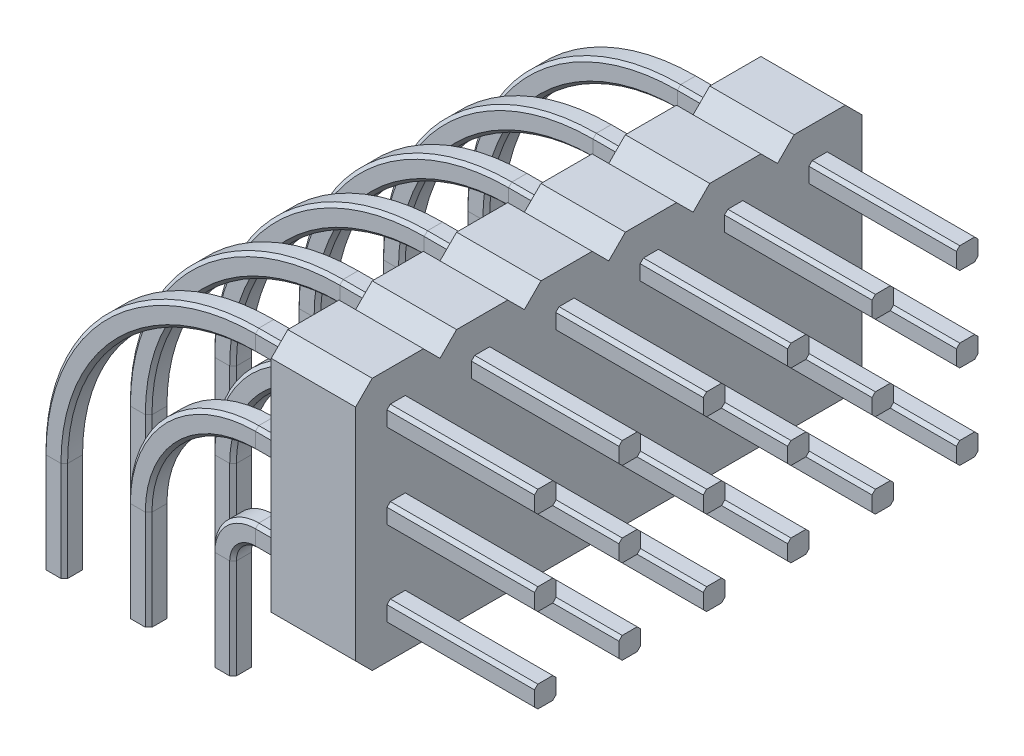
SolidWorks part; units mm, degrees
ref_plane "Front Plane" through (0, 0, 0) normal (0, 0, 1) x (1, 0, 0)
ref_plane "Top Plane" through (0, 0, 0) normal (0, 1, 0) x (1, 0, 0)
ref_plane "Right Plane" through (0, 0, 0) normal (1, 0, 0) x (0, 0, -1)
sketch "Sketch1" plane through (0, 0, 0) normal (0, 1, 0) x (1, 0, 0)
  line L0 (0.225, 0.325) -> (0.325, 0.225)
  line L1 (-0.225, 0.325) -> (0.225, 0.325)
  line L2 (-0.325, 0.225) -> (-0.325, -0.225)
  line L3 (-0.225, -0.325) -> (0.225, -0.325)
  line L4 (0.325, 0.225) -> (0.325, -0.225)
  line L5 (-0.325, 0.325) -> (0.325, -0.325) construction
  line L6 (-0.325, -0.325) -> (0.325, 0.325) construction
  line L7 (-0.325, 0.225) -> (-0.225, 0.325)
  line L8 (-0.325, -0.225) -> (-0.225, -0.325)
  line L9 (0.225, -0.325) -> (0.325, -0.225)
  line L10 (2.215, 0.225) -> (2.215, -0.225)
  line L11 (2.215, 0.225) -> (2.315, 0.325)
  line L12 (2.315, 0.325) -> (2.765, 0.325)
  line L13 (2.765, 0.325) -> (2.865, 0.225)
  line L14 (2.865, 0.225) -> (2.865, -0.225)
  line L15 (2.765, -0.325) -> (2.865, -0.225)
  line L16 (2.315, -0.325) -> (2.765, -0.325)
  line L17 (2.215, -0.225) -> (2.315, -0.325)
  line L18 (4.755, 0.225) -> (4.755, -0.225)
  line L19 (4.755, 0.225) -> (4.855, 0.325)
  line L20 (4.855, 0.325) -> (5.305, 0.325)
  line L21 (5.305, 0.325) -> (5.405, 0.225)
  line L22 (5.405, 0.225) -> (5.405, -0.225)
  line L23 (5.305, -0.325) -> (5.405, -0.225)
  line L24 (4.855, -0.325) -> (5.305, -0.325)
  line L25 (4.755, -0.225) -> (4.855, -0.325)
  point P0 (0, 0)
  dimension "D1" = 0.65
  dimension "D2" = 3
sketch "Sketch2" plane through (0, 0, 0) normal (0, 0, 1) x (1, 0, 0)
  line L0 (0, 0) -> (0, 8.08)
  line L1 (1, 9.08) -> (14.48, 9.08)
  line L2 (2.54, 0) -> (2.54, 5.54)
  line L3 (2.315, 0) -> (2.765, 0) construction
  line L4 (3.54, 6.54) -> (14.48, 6.54)
  line L5 (5.08, 0) -> (5.08, 3)
  line L6 (4.855, 0) -> (5.305, 0) construction
  line L7 (6.08, 4) -> (14.48, 4)
  arc A0 (5.08, 3) -> (6.08, 4) centre (6.08, 3) cw
  arc A1 (2.54, 5.54) -> (3.54, 6.54) centre (3.54, 5.54) cw
  arc A2 (0, 8.08) -> (1, 9.08) centre (1, 8.08) cw
  point P13 (0, 0)
  point P17 (5.08, 4)
  point P20 (2.54, 6.54)
  point P23 (0, 9.08)
  dimension "D5" = 1
  dimension "D6" = 1
  dimension "D7" = 1
  dimension "D1" = 9.08
  dimension "D2" = 14.48
  dimension "D3" = 6.54
  dimension "D4" = 4
sweep "Sweep1" add profiles "Sketch1" path "Sketch2"
ref_plane "Plane1" through (7.5, 0, 0) normal (1, 0, 0) x (0, 0, -1)
sketch "Sketch3" plane through (7.5, 0, 0) normal (1, 0, 0) x (0, 0, -1)
  line L0 (0, 9.405) -> (0, 3.675) construction
  line L1 (0.225, 9.405) -> (-0.225, 9.405) construction
  line L2 (-0.225, 3.675) -> (0.225, 3.675) construction
  line L3 (0.325, 9.08) -> (0, 9.08) construction
  line L4 (-0.77, 10.35) -> (0.77, 10.35)
  line L5 (-1.27, 9.85) -> (-1.27, 3.23)
  line L6 (-0.77, 2.73) -> (0.77, 2.73)
  line L7 (1.27, 9.85) -> (1.27, 3.23)
  line L8 (-1.27, 10.35) -> (1.27, 2.73) construction
  line L9 (-1.27, 2.73) -> (1.27, 10.35) construction
  line L10 (0.325, 8.855) -> (0.325, 9.305) construction
  line L11 (0.77, 10.35) -> (1.27, 9.85)
  line L12 (-1.27, 9.85) -> (-0.77, 10.35)
  line L13 (0.77, 2.73) -> (1.27, 3.23)
  line L14 (-1.27, 3.23) -> (-0.77, 2.73)
  point P6 (0, 6.54)
  point P15 (-12.905, 13.4273)
  dimension "D1" = 7.62
  dimension "D2" = 1.27
  dimension "D3" = 2.54
extrude "Boss-Extrude1" add sketch "Sketch3" along normal blind 2.54
pattern_linear "LPattern1" count 6 spacing 2.54 along (0, 0, -1) of bodies 104
combine bodies "Combine1" operation type add bodies to combine 104 105 106 107 108 109
